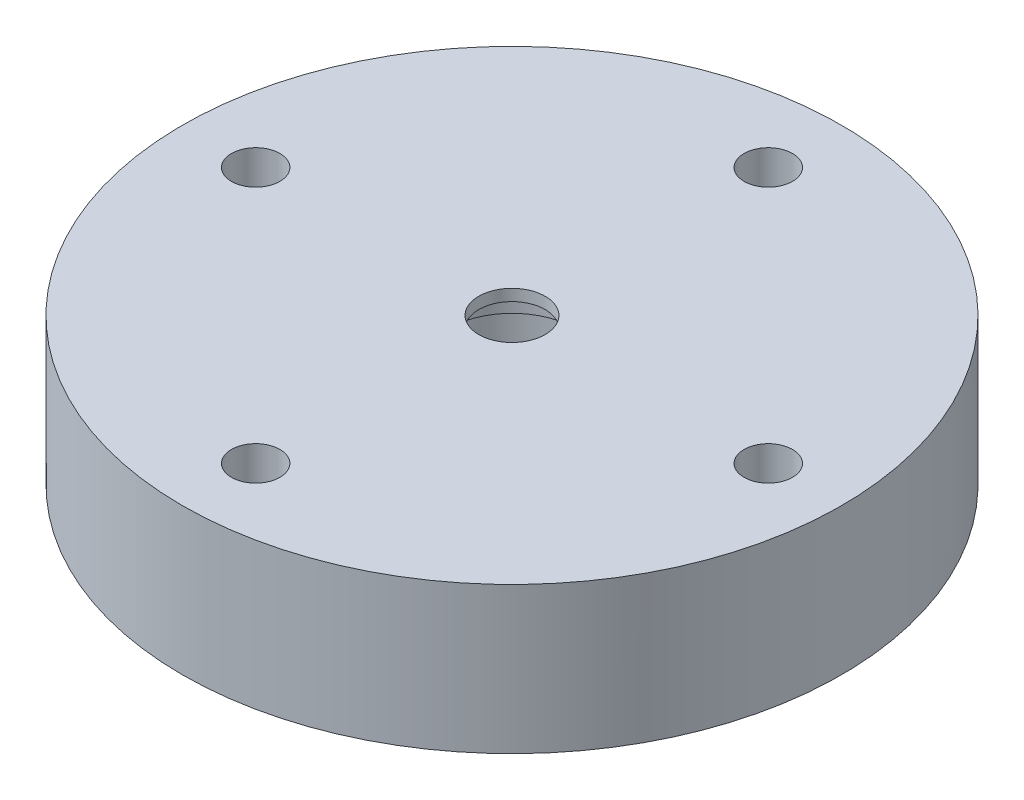
SolidWorks part; units mm, degrees
ref_plane "Front Plane" through (0, 0, 0) normal (0, 0, 1) x (1, 0, 0)
ref_plane "Top Plane" through (0, 0, 0) normal (0, 1, 0) x (1, 0, 0)
ref_plane "Right Plane" through (0, 0, 0) normal (1, 0, 0) x (0, 0, -1)
sketch "Sketch1" plane through (0, 0, 0) normal (0, 1, 0) x (1, 0, 0)
  circle A0 centre (0, 0) radius 57.15
  dimension "D1" = 114.3
extrude "seal seat hieght" add sketch "Sketch1" against normal blind 5.5372 contours A0
ref_plane "top end of seal" through (0, 0, 0) normal (0, 1, 0) x (1, 0, 0)
sketch "Sketch2" plane through (0, -5.5372, 0) normal (0, -1, 0) x (1, 0, 0)
  circle A1 centre (0, 0) radius 57.15
  circle A2 centre (0, 0) radius 57.15
  dimension "D1" = 0
extrude "seal diaphram hieght" add sketch "Sketch2" along normal blind 15.875
ref_plane "bottom end of seal" through (0, -21.4122, 0) normal (0, -1, 0) x (-1, 0, 0)
sketch "Sketch3" plane through (0, 0, 0) normal (0, 1, 0) x (1, 0, 0)
  circle A1 centre (0, 0) radius 57.15
  circle A2 centre (0, 0) radius 57.15
  dimension "D1" = 0
extrude "seal shoulder hieght" add sketch "Sketch3" along normal blind 2
sketch "Sketch4" plane through (0, -21.4122, 0) normal (0, -1, 0) x (1, 0, 0)
  circle A1 centre (0, 0) radius 57.15
  circle A2 centre (0, 0) radius 57.15
  dimension "D1" = 0
extrude "bottom seal clearance" add sketch "Sketch4" along normal blind 2
sketch "Sketch5" plane through (0, 0, 0) normal (0, 1, 0) x (1, 0, 0)
  circle A0 centre (0, 0) radius 11.1125
  dimension "D1" = 22.225
extrude "seal seat fit" cut sketch "Sketch5" against normal blind 5.5372
sketch "Sketch6" plane through (0, -21.4122, 0) normal (0, -1, 0) x (-1, 0, 0)
  circle A0 centre (0, 0) radius 12.7
  dimension "D1" = 25.4
extrude "seal diaphram clearance" cut sketch "Sketch6" against normal blind 15.875 and the other way up to surface (2 mm away) other way up to face at (0, -23.4122, -57.15)
sketch "Sketch7" plane through (0, 0, 0) normal (0, 1, 0) x (1, 0, 0)
  circle A0 centre (0, 0) radius 4.7625 construction
  circle A1 centre (0, 0) radius 5.7625
  dimension "D1" = 9.525
  dimension "D2" = 1
extrude "shaft clearance" cut sketch "Sketch7" along normal up to surface (2 mm away) up to face at (0, 2, 57.15)
sketch "bolt circle" plane through (0, 2, 0) normal (0, 1, 0) x (1, 0, 0)
  circle A0 centre (0, 0) radius 44.45 construction
  point P3 (-44.45, 0)
  point P4 (0, 44.45)
  point P5 (44.45, 0)
  point P6 (0, -44.45)
  dimension "D1" = 88.9
hole_wizard "M8 Clearance Hole1" positions "Sketch11" profile "Sketch12" hole size "M8" standard "ANSI Metric" end condition through all
sketch "Sketch11" plane through (0, 2, 0) normal (0, 1, 0) x (1, 0, 0)
  point P0 (-44.45, 0)
  point P3 (0, 44.45)
  point P6 (44.45, 0)
  point P9 (0, -44.45)
sketch "Sketch12" plane through (-44.45, 2, 0) normal (1, 0, 0) x (0, 0, 1)
  line L0 (0, 0) -> (0, 25.4122)
  line L1 (0, 25.4122) -> (4.2, 25.4122)
  line L2 (4.2, 25.4122) -> (4.2, 0)
  line L5 (4.2, 0) -> (0, 0)
  line L11 (0, -6.35) -> (0, 107.95) construction
  dimension "Thru Hole Dia." = 8.4
  dimension "Thru Hole Depth" = 25.4122
equation "\"seal seat height\"=5.5372"
equation "\"D1@seal seat hieght\" = \"seal seat height\""
equation "\"seal diaphram height\"=15.875"
equation "\"D1@seal diaphram hieght\" = \"seal diaphram height\""
equation "\"seal shoulder height\"=2"
equation "\"D1@seal shoulder hieght\" = \"seal shoulder height\""
equation "\"seal seat OD\"= .875in"
equation "\"D1@Sketch5\"=\"seal seat OD\""
equation "\"D1@seal seat fit\" = \"seal seat height\""
equation "\"seal diaphram clearance\"=25.4"
equation "\"D1@Sketch6\"=\"seal diaphram clearance\""
equation "\"D1@seal diaphram clearance\"=\"seal diaphram height\""
equation "\"seal ID\"=9.525"
equation "\"D1@Sketch7\"=\"seal ID\""
equation "\"bolt circle dia\"=88.9"
equation "\"D1@bolt circle\"=\"bolt circle dia\""
